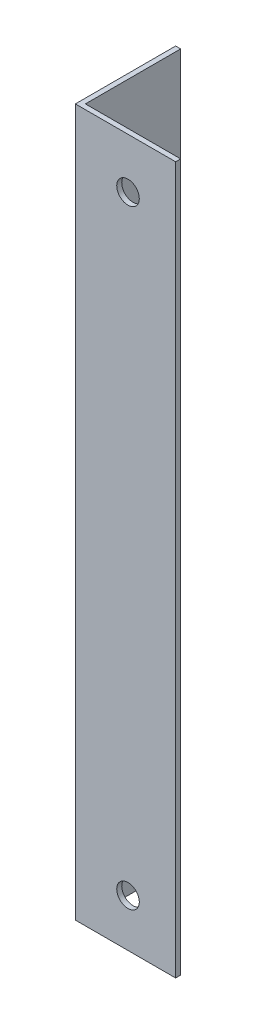
SolidWorks part; units mm, degrees
material "1060 Сплав"
ref_plane "Спереди" through (0, 0, 0) normal (0, 0, 1) x (1, 0, 0)
ref_plane "Сверху" through (0, 0, 0) normal (0, 1, 0) x (1, 0, 0)
ref_plane "Справа" through (0, 0, 0) normal (1, 0, 0) x (0, 0, -1)
sketch "Эскиз1" plane through (0, 0, 0) normal (0, 1, 0) x (1, 0, 0)
  line L0 (0, 0) -> (0, 20)
  line L1 (0, 20) -> (1, 20)
  line L2 (1, 20) -> (1, 1)
  line L3 (1, 1) -> (20, 1)
  line L4 (20, 1) -> (20, 0)
  line L5 (20, 0) -> (0, 0)
  dimension "D1" = 1
  dimension "D2" = 20
extrude "Бобышка-Вытянуть1" add sketch "Эскиз1" along normal blind 141
sketch "Эскиз2" plane through (0, 0, -1) normal (0, 0, -1) x (-1, 0, 0)
  line L0 (-10.5, 141) -> (-10.5, 0) construction
  line L1 (-20, 141) -> (-1, 141) construction
  line L2 (-20, 0) -> (-1, 0) construction
  circle A0 centre (-10.5, 131) radius 2.25
  circle A1 centre (-10.5, 9.5) radius 2.25
  dimension "D1" = 10
  dimension "D3" = 4.5
  dimension "D4" = 4.5
  dimension "D2" = 9.5
extrude "Вырез-Вытянуть1" cut sketch "Эскиз2" against normal through all
